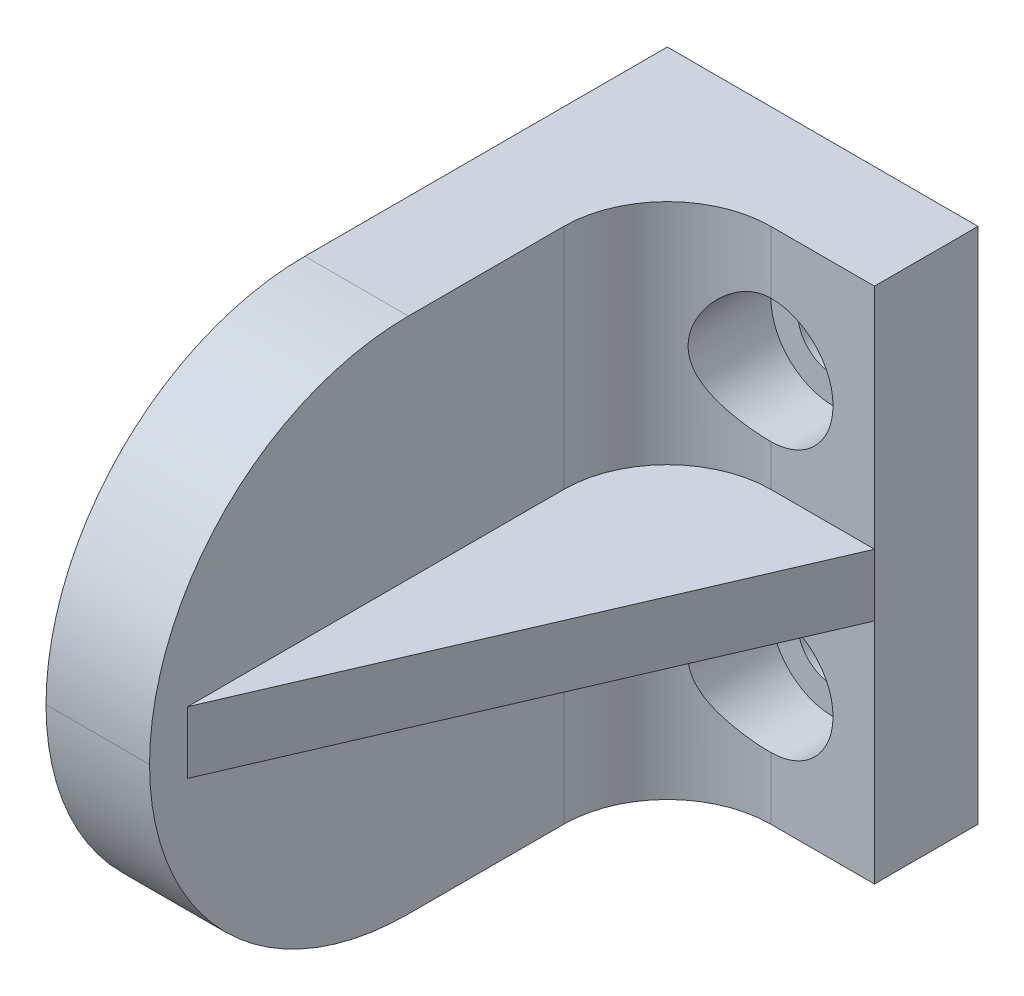
SolidWorks part; units mm, degrees
material "Custom Plastic"
ref_plane "Front Plane" through (0, 0, 0) normal (0, 0, 1) x (1, 0, 0)
ref_plane "Top Plane" through (0, 0, 0) normal (0, 1, 0) x (1, 0, 0)
ref_plane "Right Plane" through (0, 0, 0) normal (1, 0, 0) x (0, 0, -1)
sketch "Sketch1" plane through (0, 0, 0) normal (0, 0, 1) x (1, 0, 0)
  line L0 (254.0238, 235.9236) -> (254.0238, 229.9236) construction
  line L1 (264.0238, 210.9236) -> (254.0238, 210.9236)
  line L2 (264.0238, 210.9236) -> (264.0238, 235.9236)
  line L3 (264.0238, 235.9236) -> (254.0238, 235.9236)
  line L4 (264.0238, 210.9236) -> (264.0238, 235.9236)
  line L5 (264.0238, 235.9236) -> (-40.7762, 235.9236)
  line L6 (-40.7762, 235.9236) -> (-40.7762, 210.9236)
  line L7 (-40.7762, 210.9236) -> (264.0238, 210.9236)
  line L8 (264.0238, 210.9236) -> (264.0238, 235.9236)
  line L9 (264.0238, 235.9236) -> (-40.7762, 235.9236)
  line L10 (-40.7762, 235.9236) -> (-40.7762, 210.9236)
  line L11 (-40.7762, 210.9236) -> (264.0238, 210.9236)
  line L13 (254.0238, 210.9236) -> (254.0238, 216.9236) construction
  line L14 (254.0238, 216.9236) -> (259.0238, 216.9236) construction
  line L15 (254.0238, 229.9236) -> (259.0238, 229.9236)
  line L17 (264.0238, 235.9236) -> (254.0238, 235.9236)
  line L18 (264.0238, 235.9236) -> (264.0238, 210.9236)
  line L19 (264.0238, 210.9236) -> (254.0238, 210.9236)
  line L20 (254.0238, 235.9236) -> (254.0238, 210.9236)
  circle A0 centre (259.0238, 229.9236) radius 1.7
  circle A1 centre (259.0238, 216.9236) radius 1.7
  dimension "D1" = 0
extrude "Boss-Extrude1" add sketch "Sketch1" along normal blind 5 contours A0 L20 L1 L2 L3 A1 region at (259.0238, 223.4236, 0)
sketch "Sketch2" plane through (254.0238, 0, 0) normal (-1, 0, 0) x (0, 0, 1)
  line L0 (0, 235.9236) -> (30, 235.9236)
  line L2 (30, 235.9236) -> (0, 235.9236)
  line L3 (30, 235.9236) -> (30, 210.9236)
  line L4 (0, 235.9236) -> (0, 210.9236)
  line L5 (0, 210.9236) -> (5, 210.9236)
  line L6 (5, 210.9236) -> (5, 235.9236)
  line L7 (5, 235.9236) -> (0, 235.9236)
  line L8 (0, 235.9236) -> (0, 210.9236)
  line L9 (0, 210.9236) -> (5, 210.9236)
  line L10 (5, 210.9236) -> (5, 235.9236)
  line L11 (5, 235.9236) -> (0, 235.9236)
  line L12 (30, 210.9236) -> (0, 210.9236)
  line L13 (0, 235.9236) -> (0, 210.9236)
  line M5 (0, 235.9236) -> (0, 210.9236)
  line M6 (0, 210.9236) -> (5, 210.9236)
  line M7 (5, 210.9236) -> (5, 235.9236)
  line M8 (5, 235.9236) -> (0, 235.9236)
  dimension "D1" = 0
extrude "Boss-Extrude2" add sketch "Sketch2" along normal blind 5 contours L12 L3 L0 M7 | M8 M5 M6 M7 region at (254.0238, 223.4236, 2.5) region at (254.0238, 223.4236, 17.5)
sketch "Sketch3" plane through (249.0238, 0, 0) normal (-1, 0, 0) x (0, 0, 1)
  circle A0 centre (17.5, 223.4236) radius 3.95
extrude "Boss-Extrude3" add sketch "Sketch3" along normal blind 3
sketch "Sketch4" plane through (0, 0, 5) normal (0, 0, 1) x (1, 0, 0)
  circle A0 centre (259.0238, 216.9236) radius 3
  circle A1 centre (259.0238, 229.9236) radius 3
extrude "Cut-Extrude1" cut sketch "Sketch4" against normal blind 3
fillet "Fillet1" radius 12.5 2 edges at (251.5238, 210.9236, 30) (251.5238, 235.9236, 30)
ref_plane "Plane1" through (0, 223.4236, 0) normal (0, 1, 0) x (1, 0, 0)
sketch "Sketch5" plane through (0, 223.4236, 0) normal (0, 1, 0) x (1, 0, 0)
  line L4 (264.0238, -5) -> (254.0238, -28.17)
  line L6 (249.0238, 0) -> (249.0238, -17.5)
  line L7 (249.0238, -17.5) -> (254.0238, -17.5)
  line L8 (254.0238, -17.5) -> (254.0238, -5)
  line L9 (254.0238, -5) -> (264.0238, -5)
  line L10 (264.0238, -5) -> (264.0238, 0)
  line L11 (264.0238, 0) -> (249.0238, 0)
  line L12 (249.0238, 0) -> (249.0238, -17.5)
  line L13 (249.0238, -17.5) -> (254.0238, -17.5)
  line L14 (254.0238, -17.5) -> (254.0238, -5)
  line L15 (254.0238, -5) -> (264.0238, -5)
  line L16 (264.0238, -5) -> (264.0238, 0)
  line L17 (264.0238, 0) -> (249.0238, 0)
  line L20 (254.0238, -17.5) -> (249.0238, -17.5)
  line L21 (249.0238, -17.5) -> (249.0238, -30)
  line L22 (249.0238, -30) -> (254.0238, -30)
  line L23 (254.0238, -30) -> (254.0238, -17.5)
  line L24 (254.0238, -17.5) -> (249.0238, -17.5)
  line L25 (249.0238, -17.5) -> (249.0238, -30)
  line L26 (249.0238, -30) -> (254.0238, -30)
  line L27 (254.0238, -30) -> (254.0238, -17.5)
  dimension "D1" = 0
  dimension "D2" = 0
extrude "Boss-Extrude4" add sketch "Sketch5" along normal mid plane 3 contours L27 L15 L14 region at (257.3571, 223.4236, 12.7233)
fillet "Fillet2" radius 5 2 edges at (254.0238, 230.4236, 5) (254.0238, 216.4236, 5)
